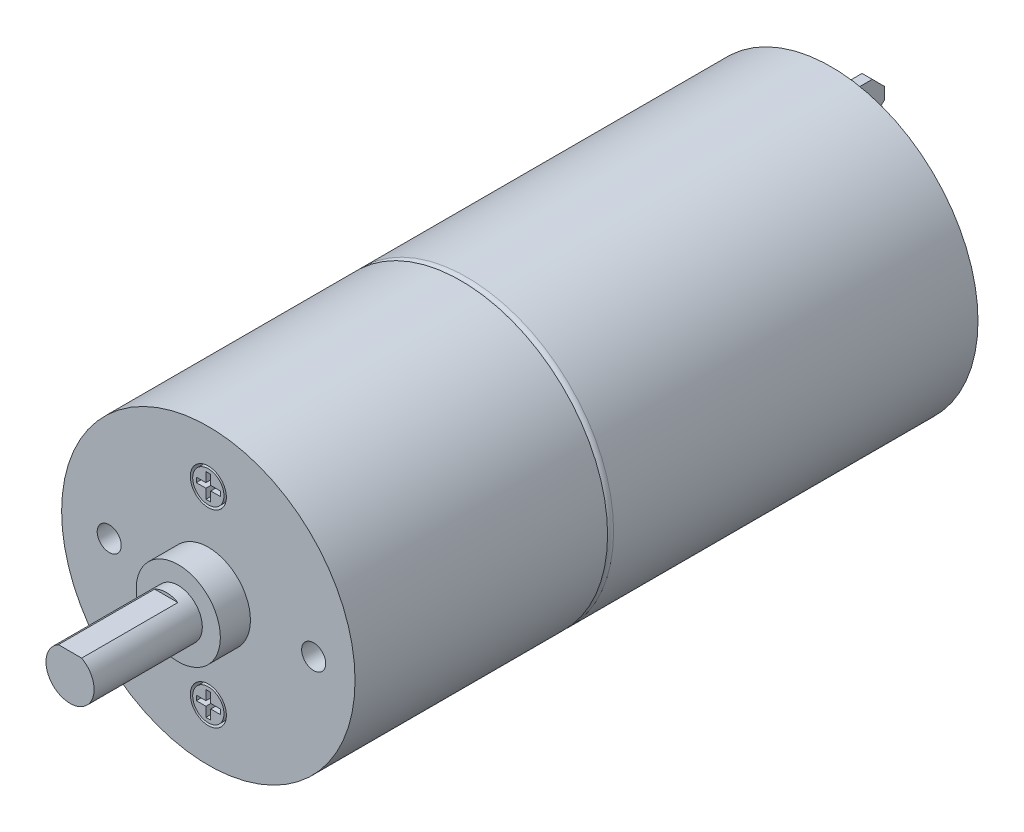
SolidWorks part; units mm, degrees
ref_plane "Ön Düzlem" through (0, 0, 0) normal (0, 0, 1) x (1, 0, 0)
ref_plane "Üst Düzlem" through (0, 0, 0) normal (0, 1, 0) x (1, 0, 0)
ref_plane "Sağ Düzlem" through (0, 0, 0) normal (1, 0, 0) x (0, 0, -1)
sketch "Çizim1" plane through (0, 0, 0) normal (0, 0, 1) x (1, 0, 0)
  circle A0 centre (-41.1435, 10.1614) radius 12.2
  dimension "D1" = 24.4
extrude "Yükseklik-Ekstrüzyon1" add sketch "Çizim1" along normal blind 30.8
fillet "Radyus1" radius 0.5 1 edges at (-28.9435, 10.1614, 30.8)
sketch "Çizim2" plane through (0, 0, 30.8) normal (0, 0, 1) x (1, 0, 0)
  circle A0 centre (-41.1435, 10.1614) radius 12.2
extrude "Yükseklik-Ekstrüzyon2" add sketch "Çizim2" along normal blind 21
sketch "Çizim3" plane through (0, 0, 51.8) normal (0, 0, 1) x (1, 0, 0)
  circle A0 centre (-41.1435, 10.1614) radius 3.5
  dimension "D1" = 7
extrude "Yükseklik-Ekstrüzyon3" add sketch "Çizim3" along normal blind 2.5
sketch "Çizim4" plane through (0, 0, 54.3) normal (0, 0, 1) x (1, 0, 0)
  circle A0 centre (-41.1435, 10.1614) radius 2
  dimension "D1" = 4
extrude "Yükseklik-Ekstrüzyon4" add sketch "Çizim4" along normal blind 9
sketch "Çizim5" plane through (0, 0, 51.8) normal (0, 0, 1) x (1, 0, 0)
  circle A0 centre (-49.3847, 10.1614) radius 1
  circle A1 centre (-32.3847, 10.1614) radius 1
  dimension "D2" = 2
  dimension "D3" = 2
  dimension "D1" = 17
extrude "Kes-Ekstrüzyon1" cut sketch "Çizim5" against normal blind 10
sketch "Çizim6" plane through (0, 0, 51.8) normal (0, 0, 1) x (1, 0, 0)
  line L0 (-40.9435, 17.0114) -> (-40.9435, 17.8114)
  line L1 (-40.9435, 19.0114) -> (-41.3435, 19.0114)
  line L2 (-41.3435, 3.3114) -> (-41.3435, 2.5114)
  line L3 (-41.3435, 1.3114) -> (-40.9435, 1.3114)
  line L4 (-40.9435, 1.3114) -> (-40.9435, 2.1114)
  line L5 (-40.9435, 3.3114) -> (-41.3435, 3.3114)
  line L6 (-41.3435, 2.5114) -> (-42.1435, 2.5114)
  line L7 (-42.1435, 2.5114) -> (-42.1435, 2.1114)
  line L8 (-42.1435, 2.1114) -> (-41.3435, 2.1114)
  line L9 (-40.1435, 2.1114) -> (-40.1435, 2.5114)
  line L10 (-40.1435, 2.5114) -> (-40.9435, 2.5114)
  line L11 (-41.3435, 2.1114) -> (-41.3435, 1.3114)
  line L12 (-40.9435, 2.5114) -> (-40.9435, 3.3114)
  line L13 (-40.9435, 2.1114) -> (-40.1435, 2.1114)
  line L14 (-41.3435, 19.0114) -> (-41.3435, 18.2114)
  line L15 (-41.3435, 17.0114) -> (-40.9435, 17.0114)
  line L16 (-40.9435, 17.8114) -> (-40.1435, 17.8114)
  line L17 (-40.1435, 17.8114) -> (-40.1435, 18.2114)
  line L18 (-40.1435, 18.2114) -> (-40.9435, 18.2114)
  line L19 (-42.1435, 18.2114) -> (-42.1435, 17.8114)
  line L20 (-42.1435, 17.8114) -> (-41.3435, 17.8114)
  line L21 (-40.9435, 18.2114) -> (-40.9435, 19.0114)
  line L22 (-41.3435, 17.8114) -> (-41.3435, 17.0114)
  line L23 (-41.3435, 18.2114) -> (-42.1435, 18.2114)
  circle A2 centre (-41.1435, 2.3114) radius 1.5
  circle A3 centre (-41.1435, 18.0114) radius 1.5
  circle A4 centre (-41.1435, 18.0114) radius 1.3
  circle A5 centre (-41.1435, 2.3114) radius 1.3
  point P34 (-41.1435, 10.1614)
  dimension "D2" = 3
  dimension "D3" = 0.2
  dimension "D4" = 2
  dimension "D5" = 0.8
  dimension "D6" = 0.8
  dimension "D7" = 0.8
  dimension "D8" = 0.8
  dimension "D9" = 0.4
  dimension "D10" = 0.4
  dimension "D11" = 0.2
  dimension "D12" = 0.2
ref_axis "Eksen1" through (-41.1435, 10.1614, 78.5769) along (0, 0, -1)
extrude "Kes-Ekstrüzyon2" cut sketch "Çizim6" against normal blind 1 contours L4 L13 L9 L10 L12 L5 L2 L6 L7 L8 L11 L3 | A2 A5 | L14 L23 L19 L20 L22 L15 L0 L16 L17 L18 L21 L1 | A3 A4 region at (-41.1435, 18.0114, 51.8) region at (-41.1435, 2.3114, 51.8) region at (-42.601, 2.3114, 51.8) region at (-42.601, 18.0114, 51.8)
sketch "Çizim8" plane through (0, 0, 63.3) normal (0, 0, 1) x (1, 0, 0)
  line L0 (-42.1117, 11.9114) -> (-40.1752, 11.9114)
  arc A0 (-40.1752, 11.9114) -> (-42.1117, 11.9114) centre (-41.1435, 10.1614) ccw
  dimension "D2" = 4
  dimension "D1" = 1.75
extrude "Kes-Ekstrüzyon3" cut sketch "Çizim8" against normal blind 8
sketch "Çizim9" plane through (0, 0, 0) normal (0, 0, -1) x (-1, 0, 0)
  circle A0 centre (41.1435, 10.1614) radius 3.25
  dimension "D1" = 6.5
extrude "Yükseklik-Ekstrüzyon5" add sketch "Çizim9" along normal blind 1
sketch "Çizim10" plane through (0, 0, -1) normal (0, 0, -1) x (-1, 0, 0)
  circle A0 centre (41.1435, 10.1614) radius 0.75
  dimension "D1" = 1.5
extrude "Yükseklik-Ekstrüzyon6" add sketch "Çizim10" along normal blind 5
sketch "Çizim11" plane through (0, 0, 0) normal (0, 0, -1) x (-1, 0, 0)
  line L3 (40.733, 20.1614) -> (41.5855, 20.1614)
  line L4 (40.733, 20.1614) -> (40.733, 17.1614)
  line L5 (40.733, 17.1614) -> (41.5855, 17.1614)
  line L6 (41.5855, 20.1614) -> (41.5855, 17.1614)
  line L7 (40.733, 3.1614) -> (41.5855, 3.1614)
  line L8 (40.733, 3.1614) -> (40.733, 0.1614)
  line L9 (40.733, 0.1614) -> (41.5855, 0.1614)
  line L10 (41.5855, 3.1614) -> (41.5855, 0.1614)
  dimension "D3" = 3
  dimension "D4" = 3
extrude "Yükseklik-Ekstrüzyon7" add sketch "Çizim11" along normal blind 4
sketch "Çizim12" plane through (-40.733, 0, 0) normal (1, 0, 0) x (0, 0, -1)
  line L0 (4, 17.1614) -> (0, 17.1614) construction
  line L1 (4, 3.1614) -> (0, 3.1614) construction
  circle A0 centre (1.9254, 18.6614) radius 0.75
  circle A1 centre (1.9254, 1.6614) radius 0.75
  dimension "D1" = 1.5
  dimension "D2" = 1.5
  dimension "D3" = 1.5
  dimension "D4" = 1.5
extrude "Kes-Ekstrüzyon4" cut sketch "Çizim12" against normal blind 4
chamfer "Pah1" distance 1 angle 45 4 edges at (-41.1593, 0.1614, -4) (-41.1593, 3.1614, -4) (-41.1593, 20.1614, -4) (-41.1593, 17.1614, -4)
